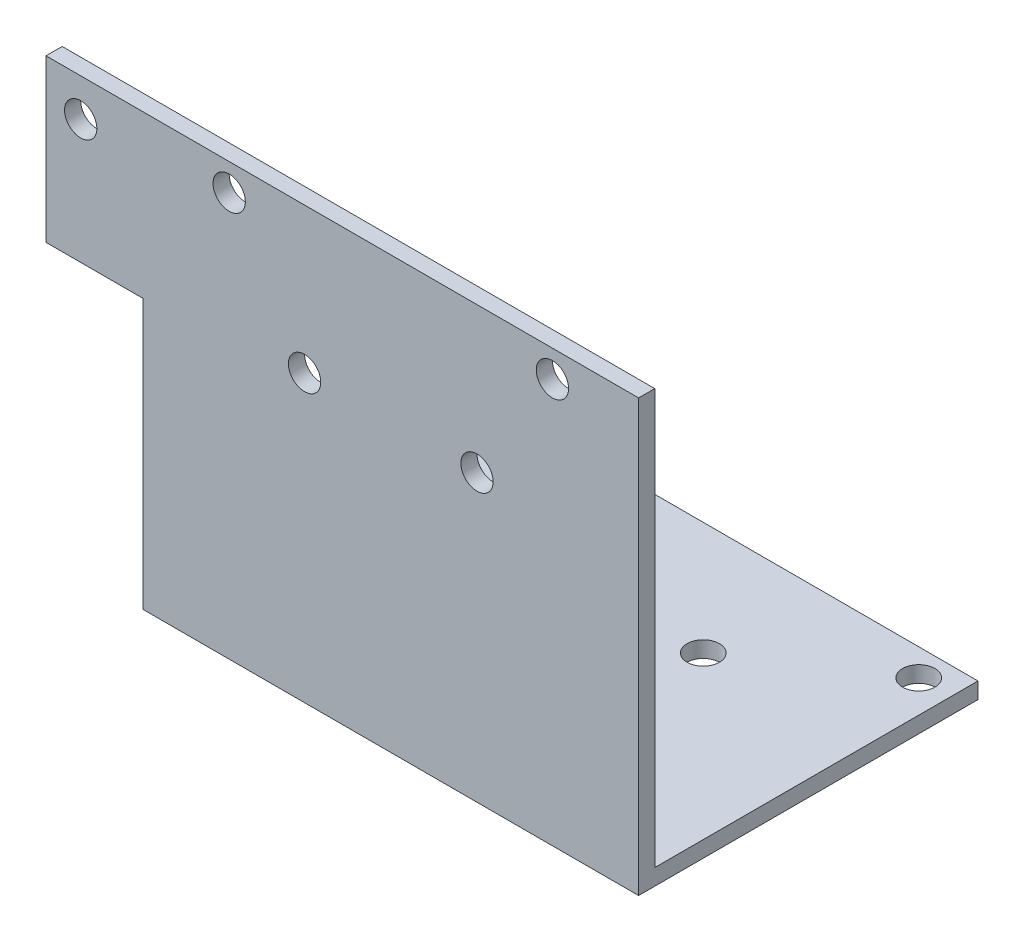
SolidWorks part; units mm, degrees
material "1060 Сплав"
ref_plane "Front" through (0, 0, 0) normal (0, 0, 1) x (1, 0, 0)
ref_plane "Top" through (0, 0, 0) normal (0, 1, 0) x (1, 0, 0)
ref_plane "Right" through (0, 0, 0) normal (1, 0, 0) x (0, 0, -1)
sketch "Эскиз1" plane through (0, 0, 0) normal (0, 0, 1) x (1, 0, 0)
  line L1 (-23, -20) -> (23, -20)
  line L2 (-23, -20) -> (-23, 20)
  line L3 (-23, 20) -> (23, 20)
  line L4 (23, -20) -> (23, 20)
  line L5 (-23, -20) -> (23, 20) construction
  line L6 (-23, 20) -> (23, -20) construction
  point P0 (0, 0)
  dimension "D1" = 40
  dimension "D2" = 46
extrude "Бобышка-Вытянуть1" add sketch "Эскиз1" along normal blind 1.5
sketch "Эскиз2" plane through (0, 0, 0) normal (0, 0, -1) x (-1, 0, 0)
  line L0 (23, 20) -> (23, -20) construction
  line L1 (-23, -20) -> (23, -20)
  line L2 (-23, -20) -> (-23, -18.5)
  line L3 (-23, -18.5) -> (23, -18.5)
  line L4 (23, -20) -> (23, -18.5)
  dimension "D1" = 1.5
extrude "Бобышка-Вытянуть2" add sketch "Эскиз2" along normal blind 30
sketch "Эскиз3" plane through (0, -18.5, 0) normal (0, 1, 0) x (1, 0, 0)
  line L0 (0, 30) -> (0, 0) construction
  line L1 (-23, 30) -> (23, 30) construction
  line L2 (23, 0) -> (-23, 0) construction
  line L3 (-8, 4.5) -> (8, 4.5) construction
  line L4 (-8, 4.5) -> (-8, 19.5) construction
  line L5 (-8, 19.5) -> (8, 19.5) construction
  line L6 (8, 4.5) -> (8, 19.5) construction
  line L7 (-8, 4.5) -> (8, 19.5) construction
  line L8 (-8, 19.5) -> (8, 4.5) construction
  line L9 (-20, 27.5) -> (20, 27.5) construction
  circle A0 centre (-8, 19.5) radius 1.5
  circle A1 centre (8, 19.5) radius 1.5
  circle A2 centre (-8, 4.5) radius 1.5
  circle A3 centre (8, 4.5) radius 1.5
  circle A4 centre (-20, 27.5) radius 1.5
  circle A5 centre (20, 27.5) radius 1.5
  point P5 (0, 12)
  point P19 (0, 27.5)
  dimension "D3" = 12
  dimension "D1" = 16
  dimension "D2" = 15
  dimension "D4" = 40
  dimension "D5" = 2.5
extrude "Вырез-Вытянуть1" cut sketch "Эскиз3" against normal up to next
sketch "Эскиз4" plane through (0, 0, 1.5) normal (0, 0, 1) x (1, 0, 0)
  line L0 (-15, 17.5) -> (15, 17.5) construction
  line L1 (0, 20) -> (0, -20) construction
  line L2 (23, 20) -> (-23, 20) construction
  line L3 (-23, -20) -> (23, -20) construction
  line L4 (0, 6.5) -> (-8, 6.5) construction
  circle A0 centre (-15, 17.5) radius 1.5
  circle A1 centre (15, 17.5) radius 1.5
  circle A2 centre (-8, 6.5) radius 1.5
  circle A3 centre (8, 6.5) radius 1.5
  point P10 (0, 17.5)
  dimension "D1" = 2.5
  dimension "D4" = 26.5
  dimension "D2" = 30
  dimension "D3" = 8
extrude "Вырез-Вытянуть2" cut sketch "Эскиз4" against normal up to next
sketch "Эскиз5" plane through (0, 0, 0) normal (0, 0, -1) x (-1, 0, 0)
  line L1 (23, 20) -> (32, 20)
  line L2 (23, 20) -> (23, 5)
  line L3 (23, 5) -> (32, 5)
  line L4 (32, 20) -> (32, 5)
  circle A0 centre (28.78, 16.5) radius 1.5
  arc A1 (15, 19) -> (14.9857, 16.0001) centre (15, 17.5) cw construction
  circle A2 centre (15, 17.5) radius 1.5 construction
  dimension "D3" = 13.78
  dimension "D1" = 9
  dimension "D2" = 15
  dimension "D4" = 1
extrude "Бобышка-Вытянуть3" add sketch "Эскиз5" against normal blind 1.5
